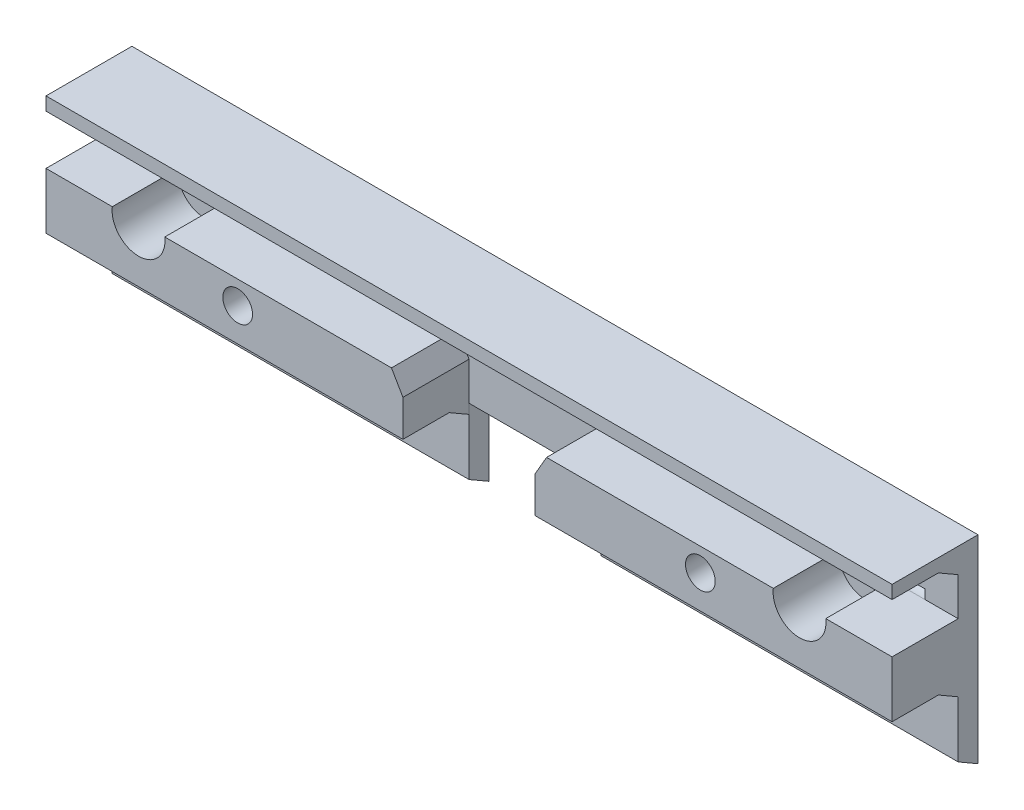
SolidWorks part; units mm, degrees
material "ABS"
ref_plane "Ebene vorne" through (0, 0, 0) normal (0, 0, 1) x (1, 0, 0)
ref_plane "Ebene oben" through (0, 0, 0) normal (0, 1, 0) x (1, 0, 0)
ref_plane "Ebene rechts" through (0, 0, 0) normal (1, 0, 0) x (0, 0, -1)
sketch "Skizze1" plane through (0, 0, 0) normal (0, 1, 0) x (1, 0, 0)
  line L0 (54, -20) -> (74, -20)
  line L1 (0, 0) -> (128, 0)
  line L2 (0, 0) -> (0, -30)
  line L3 (54, -20) -> (54, -30)
  line L4 (128, 0) -> (128, -30)
  line L5 (74, -20) -> (74, -30)
  line L6 (74, -30) -> (128, -30)
  line L7 (54, -30) -> (0, -30)
  line L8 (64, 0) -> (64, -20) construction
  line L9 (128, -10) -> (0, -10) construction
  line L10 (0, -18) -> (128, -18) construction
  line L11 (29, -13) -> (99, -13) construction
  circle A0 centre (114, -10) radius 1.65
  circle A1 centre (14, -10) radius 1.65
  circle A2 centre (29, -13) radius 2.25
  circle A3 centre (99, -13) radius 2.25
  point P23 (64, -13)
  dimension "D5" = 3.3
  dimension "D6" = 100
  dimension "D9" = 4.5
  dimension "D1" = 30
  dimension "D2" = 128
  dimension "D3" = 20
  dimension "D4" = 20
  dimension "D7" = 10
  dimension "D8" = 18
  dimension "D10" = 70
  dimension "D11" = 5
extrude "Aufsatz-Linear austragen1" add sketch "Skizze1" along normal blind 3
sketch "Skizze2" plane through (0, 3, 0) normal (0, 1, 0) x (1, 0, 0)
  line L0 (0, 0) -> (0, -30) construction
  line L1 (128, 0) -> (0, 0)
  line L2 (128, 0) -> (128, -2)
  line L3 (128, -2) -> (0, -2)
  line L4 (0, 0) -> (0, -2)
  line L5 (128, -30) -> (128, 0) construction
  line L6 (64, 0) -> (64, -20) construction
  line L7 (54, -20) -> (74, -20) construction
  line L8 (0, -9.5) -> (10.0314, -9.5)
  line L9 (0, -9.5) -> (0, -18)
  line L10 (0, -18) -> (54, -18)
  line L11 (128, -9.5) -> (128, -18)
  line L12 (128, -18) -> (74, -18)
  line L13 (74, -9.5) -> (74, -18)
  line L15 (74, -20) -> (74, -30) construction
  line L16 (74, -9.5) -> (110.0314, -9.5)
  line L17 (128, -9.5) -> (117.9686, -9.5)
  line L18 (54, -9.5) -> (17.9686, -9.5)
  line L19 (54, -9.5) -> (54, -18)
  arc A0 (110.0314, -9.5) -> (117.9686, -9.5) centre (114, -10) ccw
  circle A1 centre (114, -10) radius 1.65 construction
  arc A2 (17.9686, -9.5) -> (10.0314, -9.5) centre (14, -10) cw
  circle A3 centre (99, -13) radius 2.25 construction
  circle A4 centre (29, -13) radius 2.25 construction
  circle A5 centre (99, -13) radius 2.25
  circle A6 centre (29, -13) radius 2.25
  dimension "D4" = 4
  dimension "D1" = 9.5
  dimension "D2" = 18
  dimension "D3" = 2
extrude "Aufsatz-Linear austragen2" add sketch "Skizze2" along normal blind 10
chamfer "Fase1" distance 3 angle 30 7 edges at (54, 8, 9.5) (74, 8, 9.5) (27, 3, 18) (101, 3, 18) (27, 3, 30) (101, 3, 30)
chamfer "Fase2" distance 3 angle 30 1 edges at (64, 3, 20)
sketch "Skizze3" plane through (128, 0, 0) normal (1, 0, 0) x (0, 0, -1)
  line L0 (-9.5, 3) -> (-8.1, 3)
  line L1 (-9.5, 3) -> (-3.7321, 3) construction
  line L2 (-6.616, 3) -> (-6.616, 0) construction
  line L3 (-30, 0) -> (0, 0) construction
  line L4 (-7.1, 2) -> (-6.1321, 2)
  line L5 (-7.1, 0.6) -> (-6.1321, 0.6)
  line L6 (-3.7321, 3) -> (-5.1321, 3)
  arc A0 (-8.1, 3) -> (-7.1, 2) centre (-7.1, 3) ccw
  arc A1 (-9.5, 3) -> (-7.1, 0.6) centre (-7.1, 3) ccw
  arc A2 (-3.7321, 3) -> (-6.1321, 0.6) centre (-6.1321, 3) cw
  arc A3 (-5.1321, 3) -> (-6.1321, 2) centre (-6.1321, 3) cw
  point P17 (-6.616, 0.6)
  point P18 (-6.616, 2)
  dimension "D1" = 1.4
  dimension "D2" = 1
extrude "Schnitt-Linear austragen1" cut sketch "Skizze3" against normal blind 3 from offset 5
sketch "Skizze4" plane through (120, 0, 0) normal (1, 0, 0) x (0, 0, -1)
  line L4 (-7.1, 0.6) -> (-6.1321, 0.6)
  line L5 (-3.7321, 3) -> (-5.1321, 3)
  line L6 (-6.1321, 2) -> (-7.1, 2)
  line L7 (-8.1, 3) -> (-9.5, 3)
  line L8 (-7.1, 0.6) -> (-6.1321, 0.6)
  line L9 (-3.7321, 3) -> (-5.1321, 3)
  line L10 (-6.1321, 2) -> (-7.1, 2)
  line L11 (-8.1, 3) -> (-9.5, 3)
  arc A4 (-9.5, 3) -> (-7.1, 0.6) centre (-7.1, 3) ccw
  arc A5 (-6.1321, 0.6) -> (-3.7321, 3) centre (-6.1321, 3) ccw
  arc A6 (-6.1321, 2) -> (-5.1321, 3) centre (-6.1321, 3) ccw
  arc A7 (-8.1, 3) -> (-7.1, 2) centre (-7.1, 3) ccw
  arc A8 (-9.5, 3) -> (-7.1, 0.6) centre (-7.1, 3) ccw
  arc A9 (-6.1321, 0.6) -> (-3.7321, 3) centre (-6.1321, 3) ccw
  arc A10 (-6.1321, 2) -> (-5.1321, 3) centre (-6.1321, 3) ccw
  arc A11 (-8.1, 3) -> (-7.1, 2) centre (-7.1, 3) ccw
  dimension "D1" = 0
extrude "Schnitt-Linear austragen2" cut sketch "Skizze4" along normal blind 3 from vertex at -44.2679 starting at point (75.7321, 3, 9.5)
sketch "Skizze5" plane through (0, 0, 0) normal (-1, 0, 0) x (0, 0, 1)
  line L4 (9.5, 3) -> (8.1, 3)
  line L5 (7.1, 2) -> (6.1321, 2)
  line L6 (5.1321, 3) -> (3.7321, 3)
  line L7 (6.1321, 0.6) -> (7.1, 0.6)
  line L8 (9.5, 3) -> (8.1, 3)
  line L9 (7.1, 2) -> (6.1321, 2)
  line L10 (5.1321, 3) -> (3.7321, 3)
  line L11 (6.1321, 0.6) -> (7.1, 0.6)
  arc A4 (7.1, 0.6) -> (9.5, 3) centre (7.1, 3) ccw
  arc A5 (7.1, 2) -> (8.1, 3) centre (7.1, 3) ccw
  arc A6 (5.1321, 3) -> (6.1321, 2) centre (6.1321, 3) ccw
  arc A7 (3.7321, 3) -> (6.1321, 0.6) centre (6.1321, 3) ccw
  arc A8 (7.1, 0.6) -> (9.5, 3) centre (7.1, 3) ccw
  arc A9 (7.1, 2) -> (8.1, 3) centre (7.1, 3) ccw
  arc A10 (5.1321, 3) -> (6.1321, 2) centre (6.1321, 3) ccw
  arc A11 (3.7321, 3) -> (6.1321, 0.6) centre (6.1321, 3) ccw
  dimension "D1" = 0
extrude "Schnitt-Linear austragen3" cut sketch "Skizze5" against normal blind 3 from offset 5
sketch "Skizze6" plane through (8, 0, 0) normal (-1, 0, 0) x (0, 0, 1)
  line L4 (9.5, 3) -> (8.1, 3)
  line L5 (7.1, 2) -> (6.1321, 2)
  line L6 (5.1321, 3) -> (3.7321, 3)
  line L7 (6.1321, 0.6) -> (7.1, 0.6)
  line L8 (9.5, 3) -> (8.1, 3)
  line L9 (7.1, 2) -> (6.1321, 2)
  line L10 (5.1321, 3) -> (3.7321, 3)
  line L11 (6.1321, 0.6) -> (7.1, 0.6)
  arc A4 (7.1, 0.6) -> (9.5, 3) centre (7.1, 3) ccw
  arc A5 (7.1, 2) -> (8.1, 3) centre (7.1, 3) ccw
  arc A6 (5.1321, 3) -> (6.1321, 2) centre (6.1321, 3) ccw
  arc A7 (3.7321, 3) -> (6.1321, 0.6) centre (6.1321, 3) ccw
  arc A8 (7.1, 0.6) -> (9.5, 3) centre (7.1, 3) ccw
  arc A9 (7.1, 2) -> (8.1, 3) centre (7.1, 3) ccw
  arc A10 (5.1321, 3) -> (6.1321, 2) centre (6.1321, 3) ccw
  arc A11 (3.7321, 3) -> (6.1321, 0.6) centre (6.1321, 3) ccw
  dimension "D1" = 0
extrude "Schnitt-Linear austragen4" cut sketch "Skizze6" along normal blind 3 from vertex at -44.2679 starting at point (52.2679, 3, 9.5)
move or copy body "Körper-Verschieben/Kopieren1" bodies to move or copy 106 copy no rotation origin (0, 6.5, 15) rotation axis (1, 0, 0) rotation angle 90
